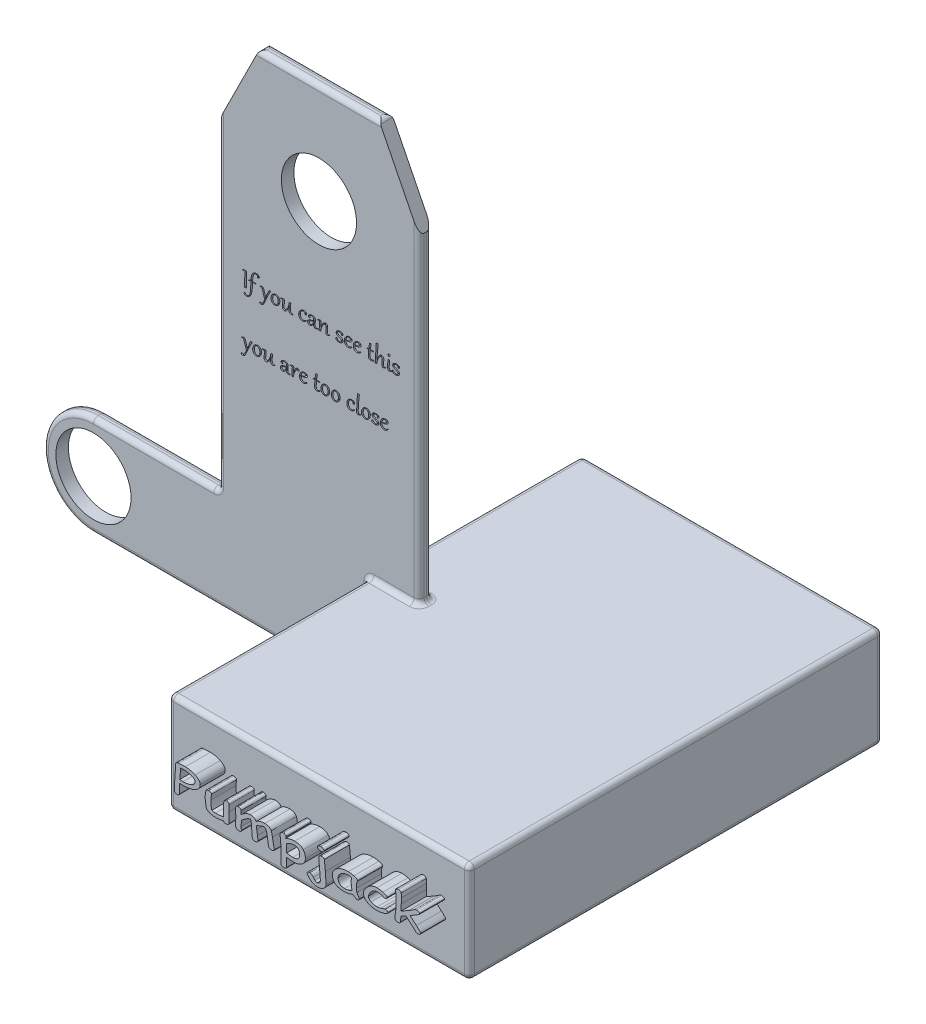
SolidWorks part; units mm, degrees
material "ABS"
ref_plane "Front Plane" through (0, 0, 0) normal (0, 0, 1) x (1, 0, 0)
ref_plane "Top Plane" through (0, 0, 0) normal (0, 1, 0) x (1, 0, 0)
ref_plane "Right Plane" through (0, 0, 0) normal (1, 0, 0) x (0, 0, -1)
sketch "Sketch1" plane through (0, 0, 0) normal (0, 0, 1) x (1, 0, 0)
  line L0 (0, 0) -> (0, -55.88) construction
  line L1 (88.9, -55.88) -> (25.4, -55.88)
  line L3 (88.9, -55.88) -> (88.9, -81.28)
  line L4 (88.9, -81.28) -> (-88.9, -81.28)
  line L5 (-88.9, -55.88) -> (-88.9, -81.28)
  line L6 (-88.9, -55.88) -> (-25.4, -55.88)
  line L8 (-25.4, -55.88) -> (-25.4, 45.72)
  line L9 (-139.7, 107.95) -> (139.7, 107.95) construction
  line L10 (-139.7, 107.95) -> (-139.7, -107.95) construction
  line L11 (-139.7, -107.95) -> (139.7, -107.95) construction
  line L12 (139.7, 107.95) -> (139.7, -107.95) construction
  line L13 (-139.7, 107.95) -> (139.7, -107.95) construction
  line L14 (-139.7, -107.95) -> (139.7, 107.95) construction
  line L15 (-25.4, 45.72) -> (25.4, 45.72)
  line L16 (25.4, 45.72) -> (25.4, -55.88)
  line L17 (-57.15, -55.88) -> (-57.15, -68.58) construction
  line L18 (0, 0) -> (0, 20.32) construction
  line L20 (-88.9, -55.88) -> (-76.2, -55.88) construction
  line L21 (-88.9, -55.88) -> (-88.9, -81.28) construction
  line L22 (-88.9, -81.28) -> (-76.2, -81.28) construction
  line L23 (-76.2, -55.88) -> (-76.2, -81.28) construction
  circle A1 centre (-57.15, -68.58) radius 9.525
  circle A3 centre (0, 20.32) radius 9.525
  point P9 (0, -81.28)
  dimension "D3" = 19.05
  dimension "D9" = 19.05
  dimension "D1" = 177.8
  dimension "D2" = 25.4
  dimension "D4" = 25.4
  dimension "D5" = 279.4
  dimension "D6" = 215.9
  dimension "D7" = 55.88
  dimension "D8" = 101.6
  dimension "D10" = 12.7
  dimension "D11" = 20.32
  dimension "D12" = 12.7
extrude "Boss-Extrude1" add sketch "Sketch1" along normal blind 3.175
sketch "Sketch4" plane through (0, 0, 3.175) normal (0, 0, 1) x (1, 0, 0)
  line L0 (-57.15, -55.88) -> (-57.15, -69.85) construction
  line L1 (-25.4, -55.88) -> (-88.9, -55.88) construction
  circle A0 centre (-57.15, -69.85) radius 1.5875
  dimension "D1" = 3.175
sketch "Sketch5" plane through (0, 0, 3.175) normal (0, 0, 1) x (1, 0, 0)
  line L0 (-88.9, -81.28) -> (88.9, -81.28) construction
  line L1 (88.9, -55.88) -> (12.7, -55.88)
  line L2 (88.9, -55.88) -> (88.9, -81.28)
  line L3 (88.9, -81.28) -> (12.7, -81.28)
  line L4 (12.7, -55.88) -> (12.7, -81.28)
  dimension "D1" = 76.2
sketch "Sketch10" plane through (0, 0, 3.175) normal (0, 0, 1) x (1, 0, 0)
  line L0 (-88.9, -81.28) -> (88.9, -81.28) construction
  line L1 (-57.15, -55.88) -> (-88.9, -55.88)
  line L2 (-88.9, -55.88) -> (-88.9, -81.28)
  line L3 (-88.9, -81.28) -> (-57.15, -81.28)
  line L4 (-25.4, 45.72) -> (-25.4, -55.88) construction
  line L5 (25.4, -55.88) -> (25.4, 45.72) construction
  line L6 (-25.4, 25.4) -> (-25.4, 45.72)
  line L7 (-25.4, 45.72) -> (-15.24, 45.72)
  line L8 (25.4, 45.72) -> (-25.4, 45.72) construction
  line L9 (-15.24, 45.72) -> (-25.4, 25.4)
  line L10 (15.24, 45.72) -> (25.4, 25.4)
  line L11 (25.4, 45.72) -> (15.24, 45.72)
  line L12 (25.4, 45.72) -> (25.4, 25.4)
  arc A0 (-57.15, -55.88) -> (-57.15, -81.28) centre (-57.15, -68.58) ccw
  dimension "D1" = 12.7
  dimension "D4" = 20.32
  dimension "D3" = 10.16
  dimension "D2" = 10.16
  dimension "D5" = 20.32
extrude "Cut-Extrude8" cut sketch "Sketch10" against normal up to next
extrude "Boss-Extrude2" add sketch "Sketch5" along normal blind 50.8
sketch "Sketch6" plane through (0, 0, 0) normal (0, 0, -1) x (-1, 0, 0)
  line L0 (57.15, -81.28) -> (-88.9, -81.28) construction
  line L1 (-88.9, -55.88) -> (-12.7, -55.88)
  line L2 (-88.9, -55.88) -> (-88.9, -81.28)
  line L3 (-88.9, -81.28) -> (-12.7, -81.28)
  line L4 (-12.7, -55.88) -> (-12.7, -81.28)
  dimension "D1" = 76.2
extrude "Boss-Extrude3" add sketch "Sketch6" along normal blind 50.8
fillet "Fillet2" radius 1.27 34 edges at (0, 45.72, 3.175) (0, 45.72, 0) (-22.225, -81.28, 3.175) (-22.225, -81.28, 0) (-41.275, -55.88, 0) (-41.275, -55.88, 3.175) (-25.4, -55.88, 1.5875) (-25.4, -15.24, 0) (-25.4, -15.24, 3.175) (25.4, -15.24, 0) (25.4, -15.24, 3.175) (25.4, -55.88, 1.5875) (19.05, -55.88, 3.175) (19.05, -55.88, 0) (12.7, -68.58, 0) (12.7, -81.28, -25.4) (12.7, -68.58, -50.8) (12.7, -55.88, -25.4) (50.8, -81.28, -50.8) (50.8, -55.88, -50.8) (88.9, -68.58, -50.8) (88.9, -55.88, 1.5875) (88.9, -81.28, 1.5875) (88.9, -68.58, 53.975) (12.7, -68.58, 3.175) (12.7, -81.28, 28.575) (12.7, -68.58, 53.975) (12.7, -55.88, 28.575) (50.8, -81.28, 53.975) (50.8, -55.88, 53.975) (-69.85, -68.58, 0) (-69.85, -68.58, 3.175) (15.24, 45.72, 1.5875) (-15.24, 45.72, 1.5875)
sketch "Sketch7" plane through (0, 0, 53.975) normal (0, 0, 1) x (1, 0, 0)
  text T0 "Pumpjack" font "Comic Sans MS" height in points 24
extrude "Boss-Extrude5" add sketch "Sketch7" along normal blind 6.35
sketch "Sketch8" plane through (0, 0, 3.175) normal (0, 0, 1) x (1, 0, 0)
  text T0 "If you can see this\r\nyou are too close" font "Gabriola" height in points 16
extrude "Cut-Extrude7" cut sketch "Sketch8" against normal up to next (3.175 mm away)
